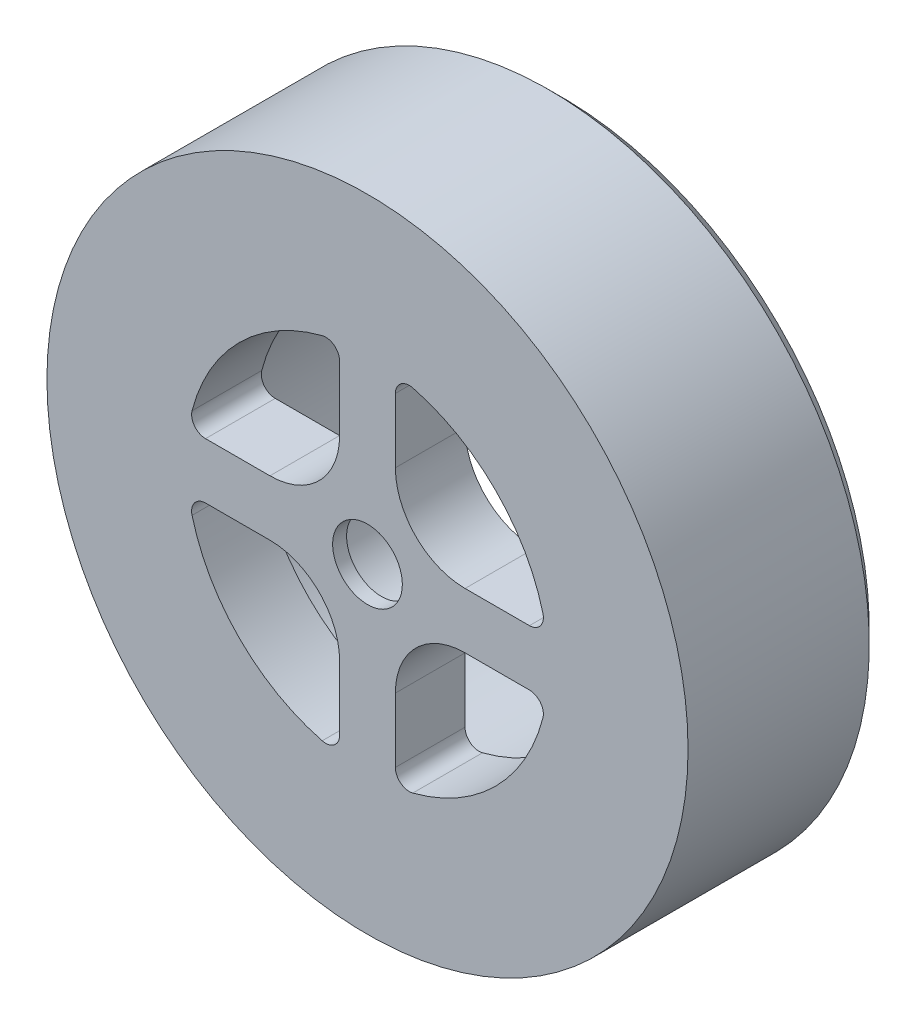
SolidWorks part; units mm, degrees
material "Liga 6061"
ref_plane "Plano frontal" through (0, 0, 0) normal (0, 0, 1) x (1, 0, 0)
ref_plane "Plano superior" through (0, 0, 0) normal (0, 1, 0) x (1, 0, 0)
ref_plane "Plano direito" through (0, 0, 0) normal (1, 0, 0) x (0, 0, -1)
sketch "Esboço1" plane through (0, 0, 0) normal (0, 0, 1) x (1, 0, 0)
  circle A0 centre (0, 0) radius 13.905
  circle A1 centre (0, 0) radius 23
extrude "Ressalto-extrusão1" add sketch "Esboço1" along normal blind 11
sketch "Esboço2" plane through (0, 0, 11) normal (0, 0, 1) x (1, 0, 0)
  circle A0 centre (0, 0) radius 23
extrude "Ressalto-extrusão2" add sketch "Esboço2" along normal blind 5
sketch "Esboço3" plane through (0, 0, 16) normal (0, 0, 1) x (1, 0, 0)
  circle A0 centre (0, 0) radius 2.5
extrude "Corte-extrusão1" cut sketch "Esboço3" against normal blind 18
sketch "Esboço4" plane through (0, 0, 11) normal (0, 0, -1) x (-1, 0, 0)
  circle A0 centre (0, 0) radius 4.5
extrude "Corte-extrusão2" cut sketch "Esboço4" against normal blind 4
sketch "Esboço5" plane through (0, 0, 16) normal (0, 0, 1) x (1, 0, 0)
  line L0 (0, 23) -> (0, -23) construction
  line L1 (-23, 0) -> (23, 0) construction
  line L2 (-2, 11.619) -> (-2, 7)
  line L4 (-11.619, 2) -> (-7, 2)
  line L5 (2, 11.619) -> (2, 7)
  line L6 (7, 2) -> (11.619, 2)
  line L8 (-23, 2) -> (23, 2) construction
  line L9 (2, -7) -> (2, -11.619)
  line L10 (-2, 23) -> (-2, -23) construction
  line L11 (7, -2) -> (11.619, -2)
  line L12 (2, 23) -> (2, -23) construction
  line L23 (-2, -7) -> (-2, -11.619)
  line L24 (-7, -2) -> (-11.619, -2)
  circle A0 centre (0, 0) radius 23 construction
  arc A1 (-2, 7) -> (-7, 2) centre (-7, 7) cw
  arc A22 (2, 7) -> (7, 2) centre (7, 7) ccw
  arc A23 (7, -2) -> (2, -7) centre (7, -7) ccw
  arc A27 (-3.25, 12.5872) -> (-12.5872, 3.25) centre (0, 0) ccw
  arc A28 (-3.25, -12.5872) -> (-2, -11.619) centre (-3, -11.619) ccw
  arc A30 (12.5872, 3.25) -> (3.25, 12.5872) centre (0, 0) ccw
  arc A31 (3.25, -12.5872) -> (12.5872, -3.25) centre (0, 0) ccw
  arc A32 (-12.5872, 3.25) -> (-11.619, 2) centre (-11.619, 3) ccw
  arc A33 (-3.25, 12.5872) -> (-2, 11.619) centre (-3, 11.619) cw
  arc A34 (3.25, 12.5872) -> (2, 11.619) centre (3, 11.619) ccw
  arc A35 (12.5872, 3.25) -> (11.619, 2) centre (11.619, 3) cw
  arc A36 (12.5872, -3.25) -> (11.619, -2) centre (11.619, -3) ccw
  arc A37 (3.25, -12.5872) -> (2, -11.619) centre (3, -11.619) cw
  arc A40 (-7, -2) -> (-2, -7) centre (-7, -7) cw
  arc A41 (-12.5872, -3.25) -> (-11.619, -2) centre (-11.619, -3) cw
  arc A42 (-3.25, -12.5872) -> (-12.5872, -3.25) centre (0, 0) cw
  point P9 (-20, -2)
  point P10 (20, -2)
  point P37 (2, -12.8452)
  point P41 (-2, 17.8885)
  point P44 (2, 17.8885)
  point P47 (17.8885, 2)
  point P50 (17.8885, -2)
  point P53 (2, -17.8885)
  dimension "D5" = 1
  dimension "D3" = 5
  dimension "D1" = 2
  dimension "D2" = 2
extrude "Corte-extrusão3" cut sketch "Esboço5" against normal blind 15
sketch "Esboço6" plane through (0, 0, 0) normal (0, 0, -1) x (-1, 0, 0)
  circle A0 centre (0, 0) radius 24.343
extrude "Corte-extrusão4" cut sketch "Esboço6" against normal blind 2
chamfer "Chanfro1" distance 1 angle 45 1 edges at (-23, 0, 2)
